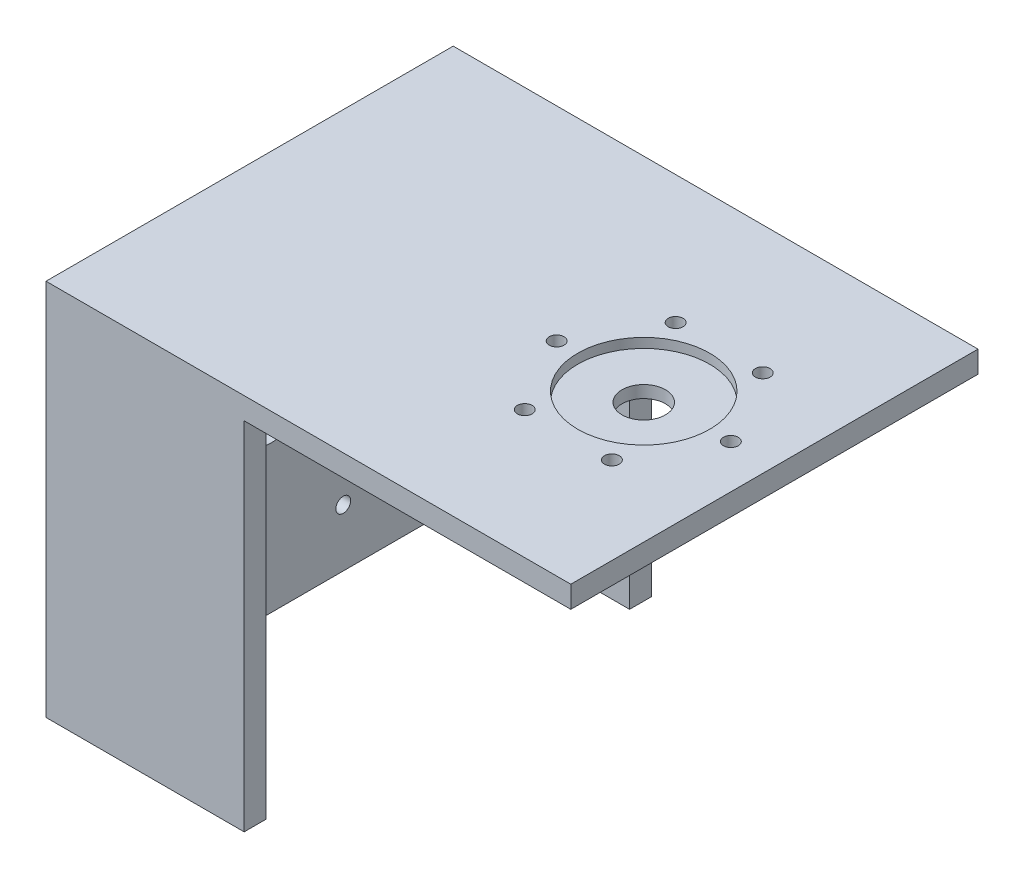
SolidWorks part; units mm, degrees
ref_plane "Front Plane" through (0, 0, 0) normal (0, 0, 1) x (1, 0, 0)
ref_plane "Top Plane" through (0, 0, 0) normal (0, 1, 0) x (1, 0, 0)
ref_plane "Right Plane" through (0, 0, 0) normal (1, 0, 0) x (0, 0, -1)
ref_plane "PL_Output_Plate_base" through (0, -5, 0) normal (0, 1, 0) x (1, 0, 0)
sketch "SK_Output_Plate" plane through (0, -5, 0) normal (0, 1, 0) x (1, 0, 0)
  line L0 (-90.5, 46.75) -> (30, 46.75)
  line L1 (30, 46.75) -> (30, -46.75)
  line L2 (30, -46.75) -> (-90.5, -46.75)
  line L3 (-90.5, -46.75) -> (-90.5, 46.75)
  circle A0 centre (20, 0) radius 1.7
  circle A1 centre (10, 17.3205) radius 1.7
  circle A2 centre (-10, 17.3205) radius 1.7
  circle A3 centre (-20, 0) radius 1.7
  circle A4 centre (-10, -17.3205) radius 1.7
  circle A5 centre (10, -17.3205) radius 1.7
  circle A6 centre (0, 0) radius 5
  dimension "D9_SK_Output_Plate" = 3.4
  dimension "D11_SK_Output_Plate" = 3.4
  dimension "D14_SK_Output_Plate" = 3.4
  dimension "D17_SK_Output_Plate" = 3.4
  dimension "D19_SK_Output_Plate" = 3.4
  dimension "D22_SK_Output_Plate" = 3.4
  dimension "D25_SK_Output_Plate" = 10
  dimension "P1" = 90.5
  dimension "P2" = 46.75
  dimension "P3" = 30
  dimension "P4" = 46.75
  dimension "P5" = 30
  dimension "P6" = 46.75
  dimension "P7" = 90.5
  dimension "P8" = 46.75
  dimension "P10" = 20
  dimension "P12" = 10
  dimension "P13" = 17.3205
  dimension "P15" = 10
  dimension "P16" = 17.3205
  dimension "P18" = 20
  dimension "P20" = 10
  dimension "P21" = 17.3205
  dimension "P23" = 10
  dimension "P24" = 17.3205
extrude "Output_Plate" add sketch "SK_Output_Plate" along normal blind 5
sketch "SK_Pitch_Pilot_Recess" plane through (0, 0, 0) normal (0, 1, 0) x (1, 0, 0)
  circle A0 centre (0, 0) radius 15.15
  dimension "D1_SK_Pitch_Pilot_Recess" = 30.3
extrude "Pitch_Pilot_Recess" cut sketch "SK_Pitch_Pilot_Recess" against normal blind 2.2
ref_plane "PL_Rear_Plate_base" through (-90.5, 0, 0) normal (1, 0, 0) x (0, 0, -1)
sketch "SK_Rear_Plate" plane through (-90.5, 0, 0) normal (1, 0, 0) x (0, 0, -1)
  line L0 (46.75, 0) -> (46.75, -86.75)
  line L1 (46.75, -86.75) -> (-46.75, -86.75)
  line L2 (-46.75, -86.75) -> (-46.75, 0)
  line L3 (-46.75, 0) -> (46.75, 0)
  circle A0 centre (0, -45) radius 8
  circle A1 centre (33, -45) radius 1.7
  circle A2 centre (16.5, -73.5788) radius 1.7
  circle A3 centre (-16.5, -73.5788) radius 1.7
  circle A4 centre (-33, -45) radius 1.7
  circle A5 centre (-16.5, -16.4212) radius 1.7
  circle A6 centre (16.5, -16.4212) radius 1.7
  dimension "D7_SK_Rear_Plate" = 16
  dimension "D9_SK_Rear_Plate" = 3.4
  dimension "D12_SK_Rear_Plate" = 3.4
  dimension "D15_SK_Rear_Plate" = 3.4
  dimension "D18_SK_Rear_Plate" = 3.4
  dimension "D21_SK_Rear_Plate" = 3.4
  dimension "D24_SK_Rear_Plate" = 3.4
  dimension "P1" = 46.75
  dimension "P2" = 46.75
  dimension "P3" = 86.75
  dimension "P4" = 46.75
  dimension "P5" = 86.75
  dimension "P6" = 46.75
  dimension "P8" = 45
  dimension "P10" = 33
  dimension "P11" = 45
  dimension "P13" = 16.5
  dimension "P14" = 73.5788
  dimension "P16" = 16.5
  dimension "P17" = 73.5788
  dimension "P19" = 33
  dimension "P20" = 45
  dimension "P22" = 16.5
  dimension "P23" = 16.4212
  dimension "P25" = 16.5
  dimension "P26" = 16.4212
extrude "Rear_Plate" add sketch "SK_Rear_Plate" along normal blind 5
ref_plane "PL_Top_Plate_base" through (0, 0, 41.75) normal (0, 0, 1) x (1, 0, 0)
sketch "SK_Top_Plate" plane through (0, 0, 41.75) normal (0, 0, 1) x (1, 0, 0)
  line L0 (-90.5, 0) -> (-45, 0)
  line L1 (-45, 0) -> (-45, -86.75)
  line L2 (-45, -86.75) -> (-90.5, -86.75)
  line L3 (-90.5, -86.75) -> (-90.5, 0)
  dimension "P1" = 90.5
  dimension "P2" = 45
  dimension "P3" = 45
  dimension "P4" = 86.75
  dimension "P5" = 90.5
  dimension "P6" = 86.75
extrude "Top_Plate" add sketch "SK_Top_Plate" along normal blind 5
ref_plane "PL_Bottom_Plate_base" through (0, 0, -46.75) normal (0, 0, 1) x (1, 0, 0)
sketch "SK_Bottom_Plate" plane through (0, 0, -46.75) normal (0, 0, 1) x (1, 0, 0)
  line L0 (-90.5, 0) -> (-45, 0)
  line L1 (-45, 0) -> (-45, -86.75)
  line L2 (-45, -86.75) -> (-90.5, -86.75)
  line L3 (-90.5, -86.75) -> (-90.5, 0)
  dimension "P1" = 90.5
  dimension "P2" = 45
  dimension "P3" = 45
  dimension "P4" = 86.75
  dimension "P5" = 90.5
  dimension "P6" = 86.75
extrude "Bottom_Plate" add sketch "SK_Bottom_Plate" along normal blind 5
equation "\"Roll_axis_y\" = 45"
equation "\"Roll_rear_x\" = -85.5"
